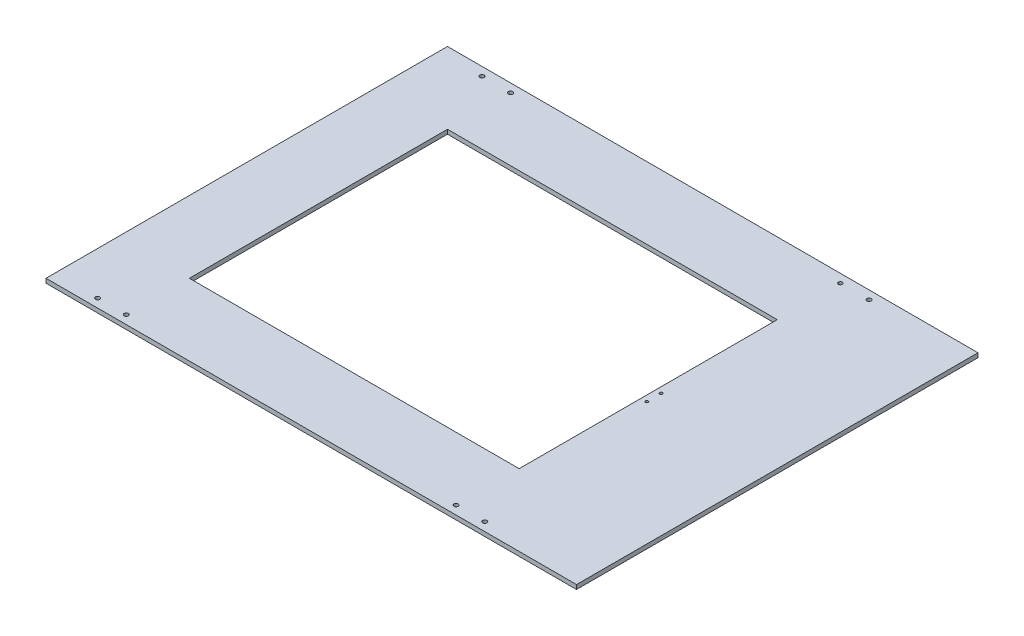
SolidWorks part; units mm, degrees
ref_plane "Front Plane" through (0, 0, 0) normal (0, 0, 1) x (1, 0, 0)
ref_plane "Top Plane" through (0, 0, 0) normal (0, 1, 0) x (1, 0, 0)
ref_plane "Right Plane" through (0, 0, 0) normal (1, 0, 0) x (0, 0, -1)
sketch "Sketch1" plane through (0, 0, 0) normal (0, 1, 0) x (1, 0, 0)
  line L1 (0, 0) -> (370, 0)
  line L2 (0, 0) -> (0, 280)
  line L3 (0, 280) -> (370, 280)
  line L4 (370, 0) -> (370, 280)
  line L5 (50, 50) -> (280, 50)
  line L6 (50, 50) -> (50, 230)
  line L7 (50, 230) -> (280, 230)
  line L8 (280, 50) -> (280, 230)
  line L9 (50, 280) -> (50, 274) construction
  line L10 (50, 274) -> (30, 274) construction
  line L12 (185, 280) -> (185, 0) construction
  line L13 (0, 140) -> (370, 140) construction
  line L14 (284, 140) -> (284, 145) construction
  line L15 (284, 140) -> (284, 135) construction
  circle A0 centre (30, 274) radius 1.5
  circle A1 centre (50, 274) radius 1.5692
  circle A2 centre (30, 6) radius 1.5
  circle A3 centre (50, 6) radius 1.5
  circle A4 centre (280, 274) radius 1.3573
  circle A5 centre (300, 274) radius 1.5
  circle A6 centre (280, 6) radius 1.5
  circle A7 centre (300, 6) radius 1.5
  circle A8 centre (284, 145) radius 1
  circle A9 centre (284, 135) radius 1
  point P9 (0, 0)
  point P10 (50, 273.2765)
  point P38 (340, 274)
  point P39 (280, 274)
  point P40 (0, 0)
  point P41 (340, 6)
  point P42 (340, 6)
  point P43 (0, 0)
  point P44 (340, 6)
  point P45 (340, 6)
  point P46 (0, 0)
  point P47 (340, 6)
  point P48 (284, 6)
  point P49 (0, 0)
  point P50 (0, 0)
  point P51 (70, 6)
  point P52 (50, 6)
  dimension "D11" = 3
  dimension "D12" = 2
  dimension "D1" = 370
  dimension "D2" = 280
  dimension "D3" = 230
  dimension "D4" = 50
  dimension "D5" = 50
  dimension "D6" = 50
  dimension "D8" = 6
  dimension "D10" = 20
  dimension "D13" = 4
  dimension "D14" = 10
  dimension "D15" = 20
  dimension "D16" = 20
  dimension "D17" = 20
extrude "Boss-Extrude1" add sketch "Sketch1" along normal blind 3
